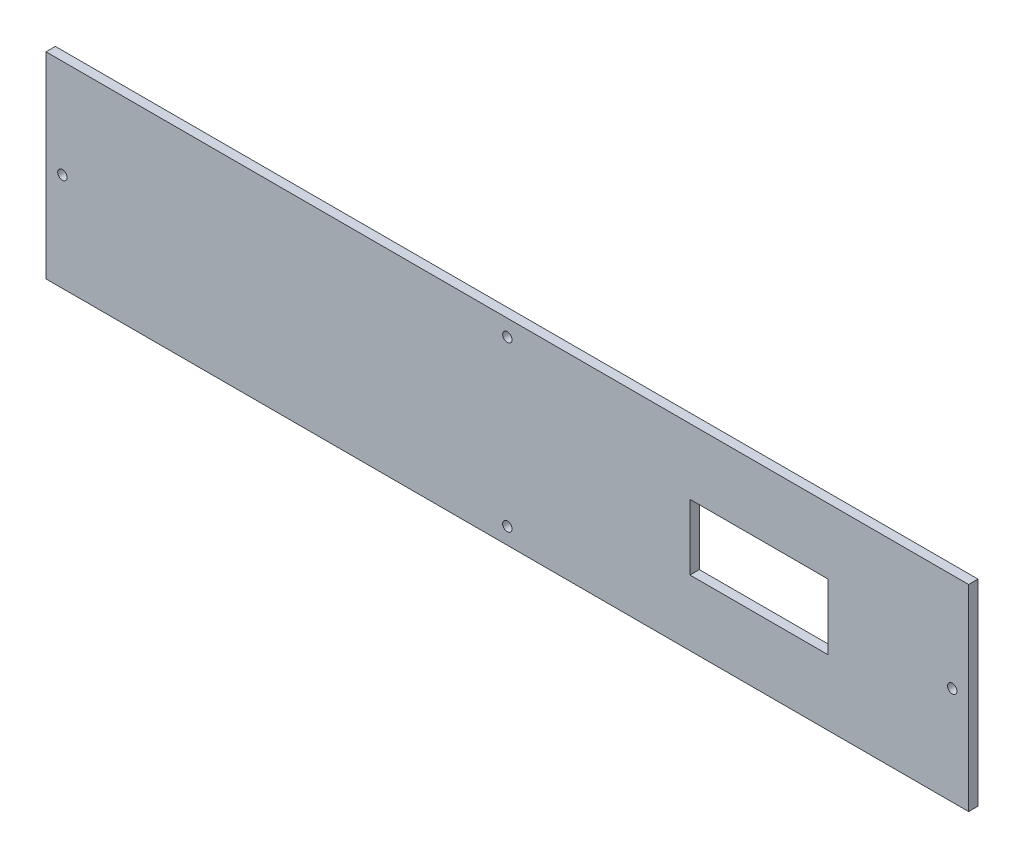
SolidWorks part; units mm, degrees
ref_plane "Piano frontale" through (0, 0, 0) normal (0, 0, 1) x (1, 0, 0)
ref_plane "Piano superiore" through (0, 0, 0) normal (0, 1, 0) x (1, 0, 0)
ref_plane "Piano destro" through (0, 0, 0) normal (1, 0, 0) x (0, 0, -1)
sketch "Schizzo1" plane through (0, 0, 0) normal (0, 0, 1) x (1, 0, 0)
  line L0 (0, 0) -> (0, 84)
  line L1 (0, 84) -> (394, 84)
  line L2 (394, 84) -> (394, 0)
  line L3 (394, 0) -> (0, 0)
  line L4 (0, 42) -> (394, 42) construction
  line L5 (197, 42) -> (197, 123.488) construction
  line L6 (275, 56) -> (275, 28)
  line L7 (275, 28) -> (334, 28)
  line L8 (334, 28) -> (334, 56)
  line L9 (334, 56) -> (275, 56)
  circle A0 centre (7, 42) radius 2
  circle A1 centre (197, 77) radius 2
  circle A2 centre (197, 7) radius 2
  circle A3 centre (387, 42) radius 2
  dimension "D3" = 7
  dimension "D4" = 7
  dimension "D6" = 4
  dimension "D1" = 84
  dimension "D2" = 394
  dimension "D5" = 60
  dimension "D7" = 59
  dimension "D8" = 28
extrude "Estrusione-Estrusione1" add sketch "Schizzo1" along normal blind 4
